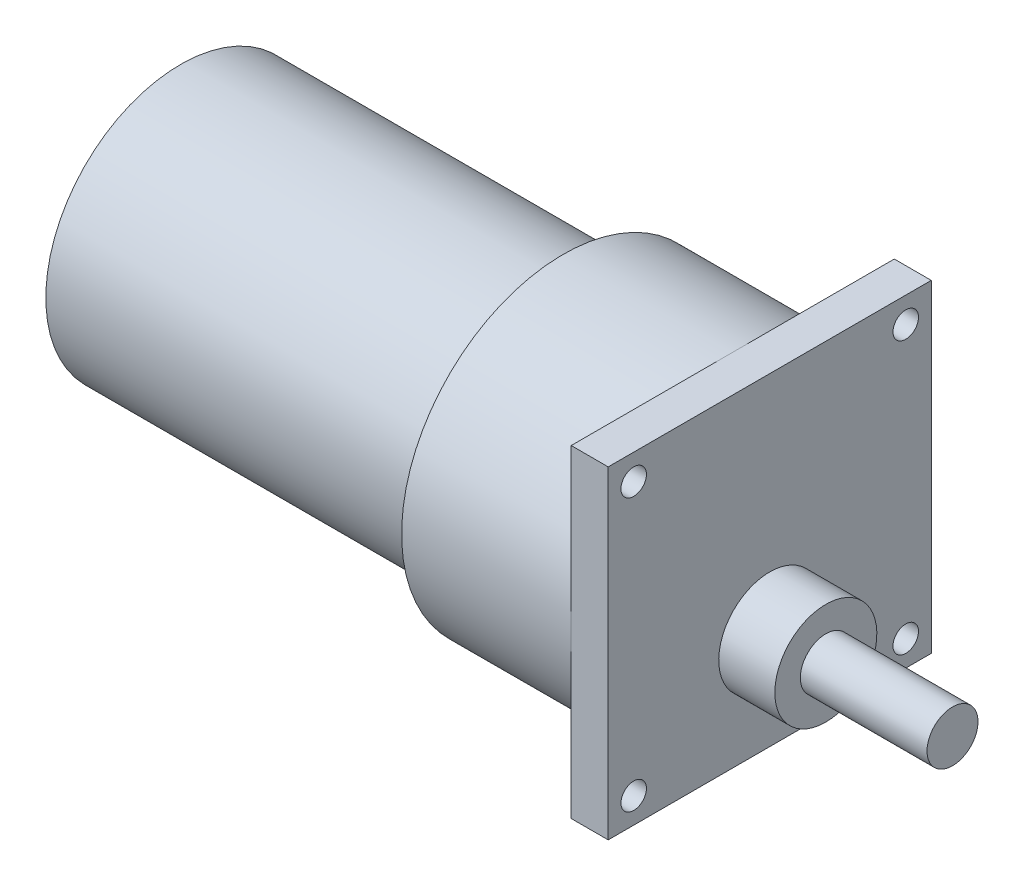
SolidWorks part; units mm, degrees
ref_plane "Front Plane" through (0, 0, 0) normal (0, 0, 1) x (1, 0, 0)
ref_plane "Top Plane" through (0, 0, 0) normal (0, 1, 0) x (1, 0, 0)
ref_plane "Right Plane" through (0, 0, 0) normal (1, 0, 0) x (0, 0, -1)
sketch "Sketch1" plane through (0, 0, 0) normal (1, 0, 0) x (0, 0, -1)
  line L1 (-19, 19) -> (19, 19)
  line L2 (-19, 19) -> (-19, -19)
  line L3 (-19, -19) -> (19, -19)
  line L4 (19, 19) -> (19, -19)
  line L5 (-19, 19) -> (19, -19) construction
  line L6 (-19, -19) -> (19, 19) construction
  circle A0 centre (0, 0) radius 19
  dimension "D1" = 38
extrude "Boss-Extrude1" add sketch "Sketch1" against normal blind 24.3 contours A0 region at (0, 0, 0)
extrude "Boss-Extrude2" add sketch "Sketch1<3>" against normal blind 4.35 contours A0 L1 L2 | A0 L4 L1 | A0 L3 L4 | A0 L2 L3 region at (0, 14.756, 14.756) region at (0, 14.756, -14.756) region at (0, -14.756, 14.756) region at (0, -14.756, -14.756)
sketch "Sketch1<3>" plane through (0, 0, 0) normal (1, 0, 0) x (0, 0, -1) same geometry as "Sketch1"
sketch "Sketch2" plane through (-24.3, 0, 0) normal (-1, 0, 0) x (0, 0, 1)
  circle A0 centre (0, 0) radius 15.85
  dimension "D1" = 31.7
extrude "Boss-Extrude3" add sketch "Sketch2" along normal blind 45
sketch "Esboço2" plane through (0, 0, 0) normal (0, 0, 1) x (1, 0, 0)
  line L0 (0, -7.2) -> (21.5, -7.2) construction
  line L1 (0, 19) -> (0, -19) construction
  line L2 (0, -1.2) -> (6.6, -1.2)
  line L3 (6.6, -1.2) -> (6.6, -4.2)
  line L4 (6.6, -4.2) -> (21.5, -4.2)
  line L5 (21.5, -4.2) -> (21.5, -7.2)
  line L6 (-4.35, -19) -> (0, -19) construction
  line L7 (0, -1.2) -> (0, -7.2)
  line L8 (0, -7.2) -> (21.5, -7.2)
  dimension "D1" = 6
  dimension "D2" = 12
  dimension "D3" = 14.9
  dimension "D4" = 6.6
  dimension "D5" = 17.8
revolve "Revolução1" add sketch "Esboço2" angle 360 about L0
sketch "Esboço3" plane through (0, 0, 0) normal (1, 0, 0) x (0, 0, -1)
  line L0 (0, 0) -> (-6.4505, 0) construction
  line L1 (0, 0) -> (0, 5.2411) construction
  line L2 (0, 0) -> (-16, 16) construction
  line L3 (-17.5, 16) -> (-19, 16) construction
  line L4 (-19, 19) -> (-19, -19) construction
  circle A0 centre (0, 0) radius 19 construction
  circle A1 centre (0, 0) radius 19 construction
  circle A2 centre (-16, 16) radius 1.5
  circle A3 centre (16, 16) radius 1.5
  circle A4 centre (16, -16) radius 1.5
  circle A5 centre (-16, -16) radius 1.5
  dimension "D2" = 3
  dimension "D1" = 45
  dimension "D3" = 1.5
extrude "Corte-extrusão1" cut sketch "Esboço3" against normal up to next contours A2 | A3 | A5 | A4 region at (0, 16, 16) region at (0, 16, -16) region at (0, -16, -16) region at (0, -16, 16)
